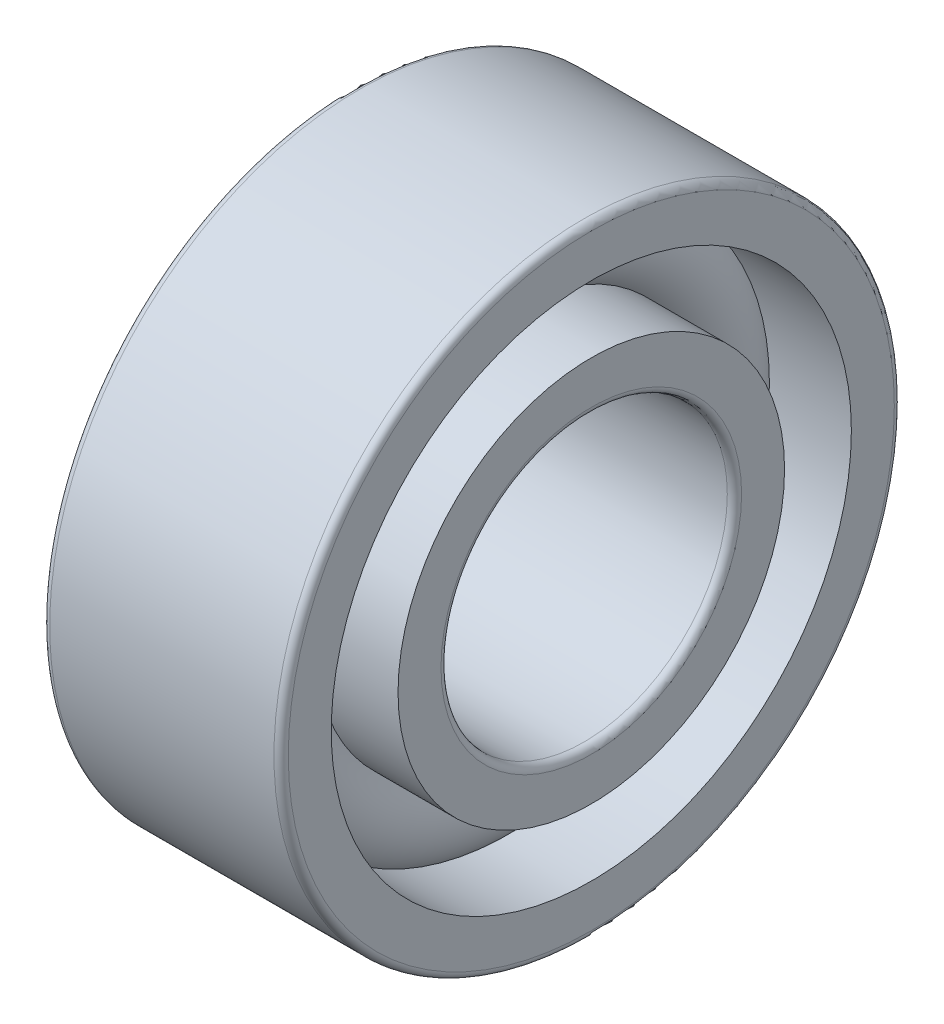
SolidWorks part; units mm, degrees
ref_plane "Plane1" through (0, 0, 0) normal (0, 0, 1) x (1, 0, 0)
ref_plane "Plane2" through (0, 0, 0) normal (0, 1, 0) x (1, 0, 0)
ref_plane "Plane3" through (0, 0, 0) normal (1, 0, 0) x (0, 0, -1)
sketch "Clipboard" plane through (0, 0, 0) normal (0, 0, 1) x (1, 0, 0)
  line L0 (-10, 0) -> (10, 0) construction
  line L1 (0, 0) -> (22.3471, -0.7804)
  line L2 (0, 0) -> (4.7471, 0.1658)
  line L3 (0, 0) -> (22.3471, -0.7804)
  line L4 (0, 0) -> (-22.3573, -0.3902)
sketch "CagSpiSke" plane through (0, 0, 0) normal (0, 0, 1) x (1, 0, 0)
  line L0 (0.105, 4.575) -> (0.105, 4.925)
  line L1 (0.105, 4.925) -> (-0.105, 4.925)
  line L2 (-0.105, 4.925) -> (-0.105, 4.575)
  line L3 (-0.105, 4.575) -> (0.105, 4.575)
  line L4 (-20.6375, 0) -> (20.6375, 0) construction
  line L5 (0, 0) -> (0, 23.7692) construction
revolve "CageSpine" add sketch "CagSpiSke" angle 0.001 about L4 reverse direction yes
ref_axis "Axis1" through (-50, 0, 0) along (1, 0, 0)
sketch "CagBalSke" plane through (0, 0, 0) normal (0, 0, 1) x (1, 0, 0)
  line L0 (-1.155, 4.75) -> (1.155, 4.75)
  line L1 (-1.905, 4.75) -> (1.905, 4.75) construction
  line L2 (-10, 0) -> (10, 0) construction
  line L3 (0, 0) -> (0, 24) construction
  arc A0 (1.155, 4.75) -> (-1.155, 4.75) centre (0, 4.75) cw
revolve "CageBall" [suppressed] add sketch "CagBalSke" angle 360 about L1 reverse direction yes
pattern_circular "CageBalls" [suppressed] count 2 every 180 about axis through (-50, 0, 0) along (1, 0, 0)
sketch "CagTrmODSke" plane through (0, 0, 0) normal (0, 0, 1) x (1, 0, 0)
  line L0 (1.156, 4.925) -> (1.156, 5.906)
  line L1 (1.156, 5.906) -> (-1.156, 5.906)
  line L2 (-1.156, 5.906) -> (-1.156, 4.925)
  line L3 (-1.156, 4.925) -> (1.156, 4.925)
  line L4 (-20.6375, 0) -> (20.6375, 0) construction
  line L5 (0, 0) -> (0, 25) construction
revolve "CageTrimOD" [suppressed] cut sketch "CagTrmODSke" angle 360 about L4 reverse direction yes
sketch "CagTrmIDSke" plane through (0, 0, 0) normal (0, 0, 1) x (1, 0, 0)
  line L0 (1.156, 3.596) -> (1.156, 4.575)
  line L1 (1.156, 4.575) -> (-1.156, 4.575)
  line L2 (-1.156, 4.575) -> (-1.156, 3.596)
  line L3 (-1.156, 3.596) -> (1.156, 3.596)
  line L4 (-20.6375, 0) -> (20.6375, 0) construction
  line L5 (0, 0) -> (0, 25) construction
revolve "CageTrimID" [suppressed] cut sketch "CagTrmIDSke" angle 360 about L4 reverse direction yes
sketch "BalSimSke" plane through (0, 0, 0) normal (0, 0, 1) x (1, 0, 0)
  line L0 (-10, 0) -> (10, 0) construction
  line L1 (-10, 4.75) -> (10, 4.75) construction
  line L2 (0, 0) -> (0, 23) construction
  circle A0 centre (0, 4.75) radius 1.05
revolve "BallsSimplified" add sketch "BalSimSke" angle 360 about L0
sketch "BalDetSke" plane through (0, 0, 0) normal (0, 0, 1) x (1, 0, 0)
  line L0 (-1.05, 4.75) -> (1.05, 4.75)
  line L1 (-1.905, 4.75) -> (1.905, 4.75) construction
  line L2 (0, 0) -> (0, 25) construction
  arc A0 (1.05, 4.75) -> (-1.05, 4.75) centre (0, 4.75) cw
revolve "BallDetailed" [suppressed] add sketch "BalDetSke" angle 360 about L1 reverse direction yes
sketch "InnRacSke" plane through (0, 0, 0) normal (0, 0, 1) x (1, 0, 0)
  line L0 (-0.7487, 4.05) -> (-2.5, 4.05)
  line L1 (-2.5, 4.05) -> (-2.5, 3.15)
  line L2 (-2.35, 3) -> (2.35, 3)
  line L3 (2.5, 3.15) -> (2.5, 4.05)
  line L4 (2.5, 4.05) -> (0.7487, 4.05)
  line L5 (-20.6375, 0) -> (20.6375, 0) construction
  line L6 (0, 0) -> (0, 30) construction
  arc A0 (-2.5, 3.15) -> (-2.35, 3) centre (-2.35, 3.15) ccw
  arc A1 (2.35, 3) -> (2.5, 3.15) centre (2.35, 3.15) ccw
  arc A2 (0.7487, 4.05) -> (-0.7487, 4.05) centre (0, 4.75) cw
revolve "InnerRace" add sketch "InnRacSke" angle 360 about L5 reverse direction yes
sketch "OutRacSke" plane through (0, 0, 0) normal (0, 0, 1) x (1, 0, 0)
  line L0 (-0.7487, 5.45) -> (-2.5, 5.45)
  line L1 (-2.5, 5.45) -> (-2.5, 6.35)
  line L2 (-2.35, 6.5) -> (2.35, 6.5)
  line L3 (2.5, 6.35) -> (2.5, 5.45)
  line L4 (2.5, 5.45) -> (0.7487, 5.45)
  line L5 (-20.6375, 0) -> (20.6375, 0) construction
  line L6 (0, 0) -> (0, 30) construction
  arc A0 (-2.5, 6.35) -> (-2.35, 6.5) centre (-2.35, 6.35) cw
  arc A1 (2.35, 6.5) -> (2.5, 6.35) centre (2.35, 6.35) cw
  arc A2 (0.7487, 5.45) -> (-0.7487, 5.45) centre (0, 4.75) ccw
revolve "OuterRace" add sketch "OutRacSke" angle 360 about L5 reverse direction yes
pattern_circular "BallsDetailed" [suppressed] count 2 every 180 about axis through (-50, 0, 0) along (1, 0, 0)
equation "\"BallCLRad@Clipboard\" = ( \"OD@OutRacSke\" + \"ID@InnRacSke\" ) / 4"
equation "\"BallCLRad@BalSimSke\" = \"BallCLRad@Clipboard\""
equation "\"BallCLRad@BalDetSke\" = \"BallCLRad@Clipboard\""
equation "\"BallCLRad@InnRacSke\" = \"BallCLRad@Clipboard\""
equation "\"BallCLRad@OutRacSke\" = \"BallCLRad@Clipboard\""
equation "\"Ball_diameter@InnRacSke\" = \"Ball_diameter@BalDetSke\" - 0.05"
equation "\"Ball_diameter@OutRacSke\" = \"Ball_diameter@BalDetSke\" - 0.05"
equation "\"Ball_diameter@BalSimSke\" = \"Ball_diameter@BalDetSke\""
equation "\"Width@OutRacSke\" = \"Width@InnRacSke\""
equation "\"Fillet_radius@OutRacSke\" = \"Fillet_radius@InnRacSke\""
equation "\"Max_count@Clipboard\" = int( 3.14159265 / atn(( \"Ball_diameter@BalDetSke\" / 2) / sqr( \"BallCLRad@Clipboard\"  *  \"BallCLRad@Clipboard\" - ( \"Ball_diameter@BalDetSke\" / 2) *  ( \"Ball_diameter@BalDetSke\" / 2))))"
equation "\"Max_count@Clipboard\" = ((sgn( \"Max_count@Clipboard\" - \"Count@Clipboard\" )-1)*( \"Max_count@Clipboard\" - \"Count@Clipboard\" ))/-2+ \"Count@Clipboard\""
equation "\"Count@BallsDetailed\" = int( \"Show_count@Clipboard\" ) "
equation "\"Count@BallsDetailed\" = ((sgn( \"Count@BallsDetailed\" - \"Max_count@Clipboard\" )-1)*( \"Count@BallsDetailed\" - \"Max_count@Clipboard\" ))/-2+ \"Max_count@Clipboard\""
equation "\"Count@BallsDetailed\" = ((sgn( \"Count@BallsDetailed\" - \"Min_count@Clipboard\" )+1)*( \"Count@BallsDetailed\" - \"Min_count@Clipboard\"))/2 +\"Min_count@Clipboard\""
equation "\"Angle@BallsDetailed\" = 360.0 / \"Max_count@Clipboard\""
equation "\"BallCLRad@CagBalSke\" = \"BallCLRad@Clipboard\""
equation "\"Count@CageBalls\" = \"Count@BallsDetailed\""
equation "\"Angle@CageBalls\" = \"Angle@BallsDetailed\""
equation "\"Angle@CageSpine\" =  \"Angle@CageBalls\" * ( \"Count@CageBalls\" -1 + int( \"Count@CageBalls\" / \"Max_count@Clipboard\" ) )  + 0.001 -  int( \"Count@CageBalls\" / \"Max_count@Clipboard\" ) * 0.001"
equation "\"Angle@CageSpine\" =  \"Angle@CageSpine\" * int( \"Min_count@Clipboard\" / 2) + int(1 / \"Min_count@Clipboard\")  * 0.001"
equation "\"CageWallOD@CagBalSke\" =  \"Ball_diameter@BalDetSke\" * 1.1"
equation "\"Thickness@CagSpiSke\" =  \"Ball_diameter@BalDetSke\" * 0.1"
equation "\"OD@CagTrmODSke\" = \"BallCLRad@Clipboard\" * 2 + \"CageWallOD@CagBalSke\" + 0.002"
equation "\"ID@CagTrmODSke\" = \"BallCLRad@Clipboard\" * 2 + \"Ball_diameter@BalDetSke\" / 6"
equation "\"OD@CagTrmIDSke\" = \"BallCLRad@Clipboard\" * 2 - \"Ball_diameter@BalDetSke\" / 6"
equation "\"ID@CagTrmIDSke\" = \"BallCLRad@Clipboard\" * 2 - \"CageWallOD@CagBalSke\" + 0.002"
equation "\"OD@CagSpiSke\" = \"ID@CagTrmODSke\""
equation "\"ID@CagSpiSke\" = \"OD@CagTrmIDSke\""
equation "\"Width@CagTrmODSke\" = \"CageWallOD@CagBalSke\" + 0.002"
equation "\"Width@CagTrmIDSke\" = \"CageWallOD@CagBalSke\" + 0.002"
